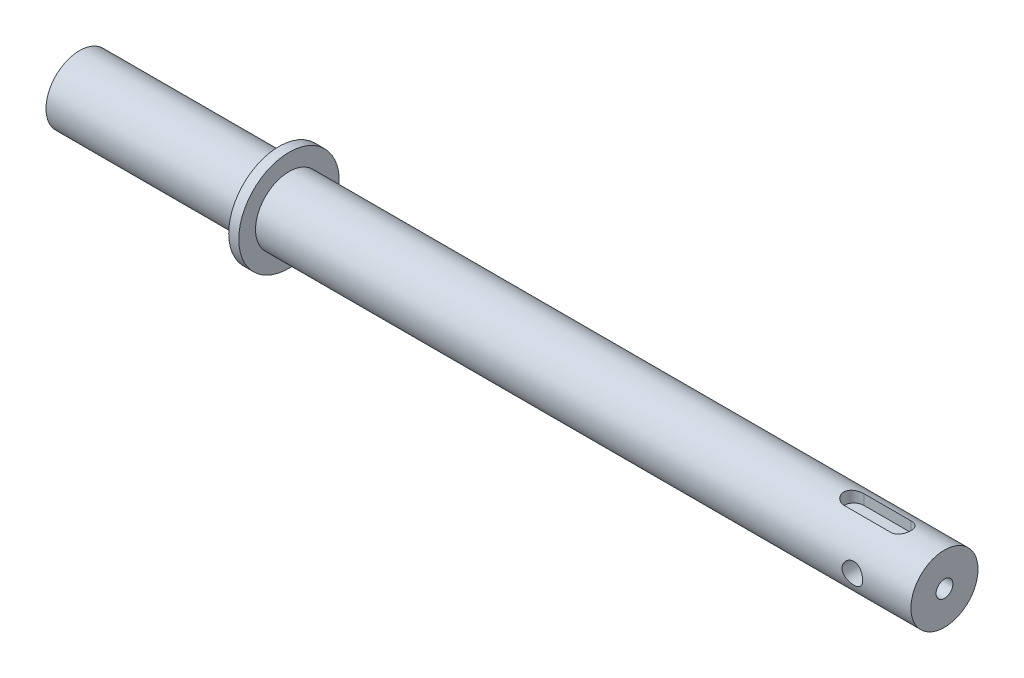
SolidWorks part; units mm, degrees
ref_plane "Alzado" through (0, 0, 0) normal (0, 0, 1) x (1, 0, 0)
ref_plane "Planta" through (0, 0, 0) normal (0, 1, 0) x (1, 0, 0)
ref_plane "Vista lateral" through (0, 0, 0) normal (1, 0, 0) x (0, 0, -1)
sketch "Croquis1" plane through (0, 0, 0) normal (1, 0, 0) x (0, 0, -1)
  circle A0 centre (0, 0) radius 10
  dimension "D1" = 20
extrude "Saliente-Extruir1" add sketch "Croquis1" along normal blind 258 from offset 8
ref_plane "Plano1" through (70.5, 0, 0) normal (-1, 0, 0) x (0, 0, 1)
sketch "Croquis2" plane through (70.5, 0, 0) normal (-1, 0, 0) x (0, 0, 1)
  circle A0 centre (0, 0) radius 15
  dimension "D1" = 30
extrude "Saliente-Extruir2" add sketch "Croquis2" along normal blind 3
sketch "Croquis3" plane through (0, 0, 0) normal (0, 0, 1) x (1, 0, 0)
  circle A0 centre (248.5, 0) radius 3.075
  dimension "D1" = 6.15
extrude "Cortar-Extruir1" cut sketch "Croquis3" against normal up to next and the other way up to next
sketch "Croquis4" plane through (0, 0, 0) normal (0, 1, 0) x (1, 0, 0)
  line L0 (266, 0) -> (231.4531, 0) construction
  line L1 (266, -10) -> (266, 10) construction
  line L2 (239, 0) -> (253, 0) construction
  line L3 (239, 3) -> (253, 3)
  line L4 (239, -3) -> (253, -3)
  arc A0 (239, 3) -> (239, -3) centre (239, 0) ccw
  arc A1 (253, -3) -> (253, 3) centre (253, 0) ccw
  point P7 (246, 0)
  dimension "D1" = 6
  dimension "D2" = 20
  dimension "D3" = 14
extrude "Cortar-Extruir2" cut sketch "Croquis4" against normal blind 3.5 from offset 10
hole_wizard "Taladro roscado M61" positions "Croquis3D2" profile "Croquis7" tap size "M6" standard "DIN"
sketch3d "Croquis3D2"
  circle A0 centre (266, 0, 0) radius 10 construction
  point P0 (266, 0, 0)
  point P5 (276, 0, 0)
sketch "Croquis7" plane through (266, 0, 0) normal (0, 1, 0) x (0, 0, -1)
  line L0 (0, 0) -> (0, 13)
  line L1 (0, 13) -> (2.5, 11.4978)
  line L2 (2.5, 11.4978) -> (2.5, 0)
  line L5 (2.5, 0) -> (0, 0)
  line L10 (0, 13) -> (-2.5, 11.4978) construction
  line L11 (0, -6.35) -> (0, 107.95) construction
  dimension "Diámetro de perforador para roscar" = 5
  dimension "Profundidad de perforador para roscar" = 13
  dimension "Ángulo de perforador" = 118
cosmetic thread "Rosca de taladro1" parameters "D1"=12, "D2"=6
